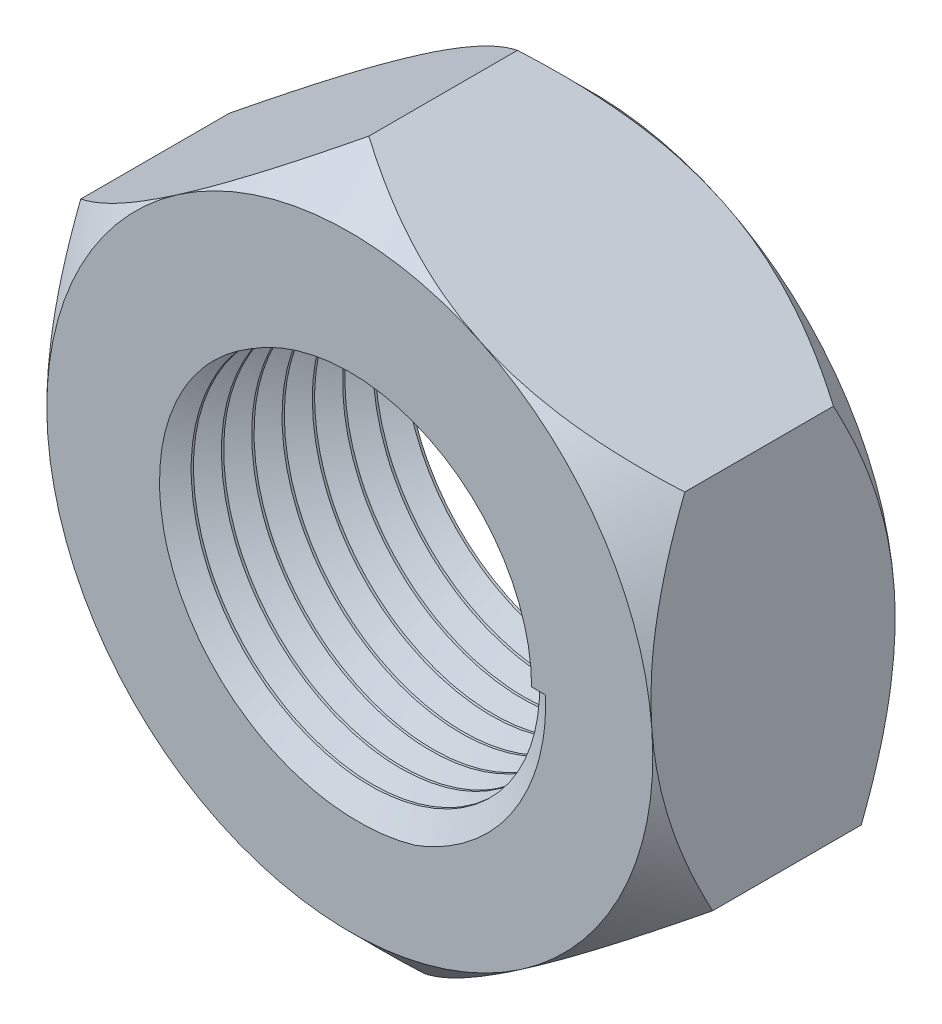
SolidWorks part; units mm, degrees
ref_plane "Plan de face" through (0, 0, 0) normal (0, 0, 1) x (1, 0, 0)
ref_plane "Plan de dessus" through (0, 0, 0) normal (0, 1, 0) x (1, 0, 0)
ref_plane "Plan de droite" through (0, 0, 0) normal (1, 0, 0) x (0, 0, -1)
sketch "Esquisse1" plane through (0, 0, 0) normal (0, 0, 1) x (1, 0, 0)
  line L1 (2.3771, 1.6379) -> (-0.2299, 2.8776)
  line L2 (-0.2299, 2.8776) -> (-2.607, 1.2397)
  line L3 (-2.607, 1.2397) -> (-2.3771, -1.6379)
  line L4 (-2.3771, -1.6379) -> (0.2299, -2.8776)
  line L5 (0.2299, -2.8776) -> (2.607, -1.2397)
  line L6 (2.607, -1.2397) -> (2.3771, 1.6379)
  circle A0 centre (0, 0) radius 2.5 construction
  circle A1 centre (0, 0) radius 1.5
  dimension "D1" = 3
  dimension "D2" = 5
extrude "Boss.-Extru.1" add sketch "Esquisse1" along normal mid plane 2
sketch "Esquisse2" plane through (0, 0, 1) normal (0, 0, 1) x (1, 0, 0)
  circle A0 centre (0, 0) radius 6
curve "Hélice/Spirale1" pitch 0.25 height 15 turns 60
sketch "Esquisse3" plane through (0, 0, 0) normal (0, 1, 0) x (1, 0, 0)
  line L0 (0, 0) -> (0, 8.1523) construction
  line L1 (-1.7, 9.8257) -> (-1.325, 9.6092)
  line L2 (-1.325, 9.6092) -> (-1.325, 10.0422)
  line L3 (-1.325, 10.0422) -> (-1.7, 9.8257)
  circle A0 centre (-1.45, 9.8257) radius 0.125 construction
  dimension "D3" = 0.25
  dimension "D1" = 9.8257
  dimension "D2" = 1.45
sweep "Enlèvement de matière-Balayage1" cut profiles "Esquisse3" path "Hélice/Spirale1"
sketch "Esquisse4" plane through (0, 0, 1) normal (0, 0, 1) x (1, 0, 0)
  circle A0 centre (0, 0) radius 2.5
  dimension "D1" = 5
extrude "Enlèv. mat.-Extru.1" cut sketch "Esquisse4" against normal blind 10 draft 45 flip side to cut
mirror "Symétrie1" about plane through (0, 0, 0) normal (0, 0, 1) of "Enlèv. mat.-Extru.1"
